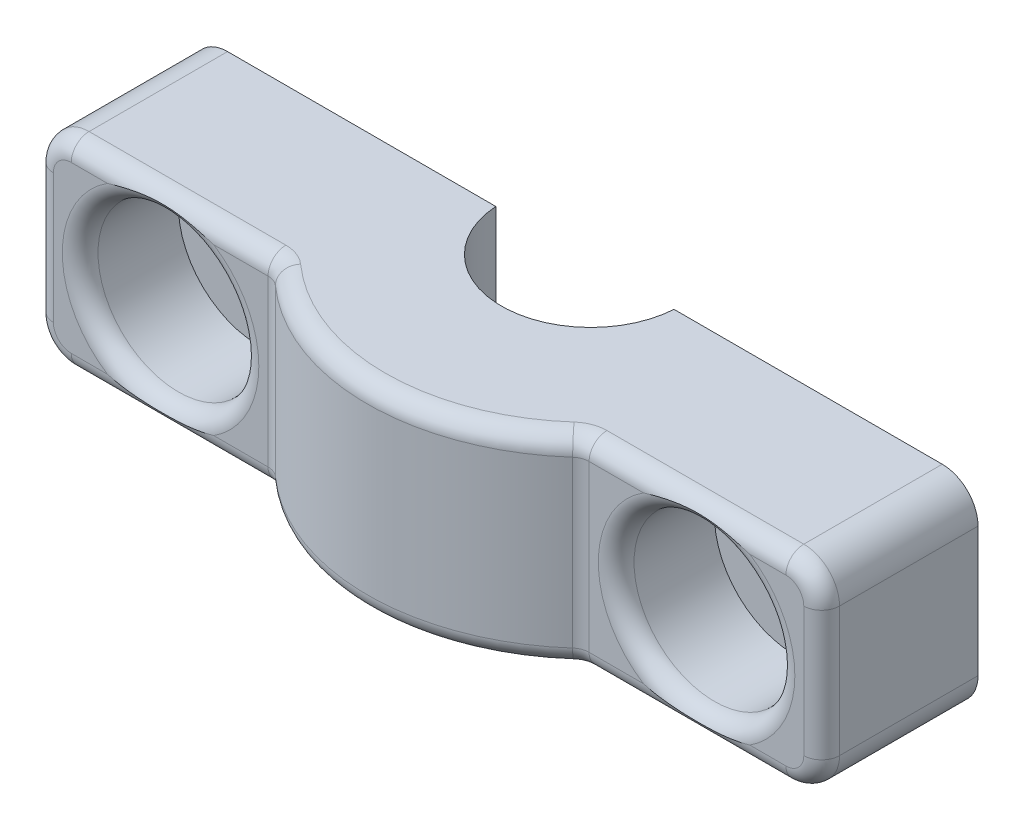
SolidWorks part; units mm, degrees
ref_plane "Front Plane" through (0, 0, 0) normal (0, 0, 1) x (1, 0, 0)
ref_plane "Top Plane" through (0, 0, 0) normal (0, 1, 0) x (1, 0, 0)
ref_plane "Right Plane" through (0, 0, 0) normal (1, 0, 0) x (0, 0, -1)
sketch "Sketch2" plane through (0, 0, 0) normal (0, 1, 0) x (1, 0, 0)
  line L0 (4.9994, -0.0762) -> (21.9999, -0.0762)
  line L1 (21.9999, -0.0762) -> (21.9999, -9.0762)
  line L2 (21.9999, -9.0762) -> (8.5949, -9.0762)
  line L3 (-4.9994, -0.0762) -> (-21.9999, -0.0762)
  line L4 (-21.9999, -0.0762) -> (-21.9999, -9.0762)
  line L5 (-21.9999, -9.0762) -> (-8.5949, -9.0762)
  arc A0 (-4.9994, -0.0762) -> (4.9994, -0.0762) centre (0, 0) ccw
  arc A1 (-8.5949, -9.0762) -> (8.5949, -9.0762) centre (0, 0) ccw
  dimension "D1" = 10
  dimension "D2" = 25
  dimension "D3" = 22
  dimension "D4" = 22
  dimension "D5" = 9
extrude "Boss-Extrude2" add sketch "Sketch2" along normal blind 11.25
sketch "Sketch3" plane through (0, 0, 9.0762) normal (0, 0, 1) x (1, 0, 0)
  line L0 (21.9999, 5.625) -> (-21.9999, 5.625) construction
  line L1 (21.9999, 11.25) -> (21.9999, 0) construction
  line L2 (-21.9999, 11.25) -> (-21.9999, 0) construction
  line L3 (8.5949, 11.25) -> (-8.5949, 11.25) construction
  line L4 (4.9994, 11.25) -> (-4.9994, 11.25) construction
  circle A0 centre (15, 5.625) radius 1.75
  circle A1 centre (-15, 5.625) radius 1.75
  point P10 (0, 11.25)
  point P13 (0, 11.25)
  dimension "D1" = 3.5
  dimension "D2" = 15
  dimension "D3" = 15
extrude "Cut-Extrude1" cut sketch "Sketch3" against normal blind 15
sketch "Sketch4" plane through (0, 0, 9.0762) normal (0, 0, 1) x (1, 0, 0)
  circle A0 centre (15, 5.625) radius 4.5
  circle A1 centre (-15, 5.625) radius 4.5
  dimension "D1" = 9
extrude "Cut-Extrude2" cut sketch "Sketch4" against normal offset from surface (5.5 mm away) 3.5 up to face at (16.75, 5.625, 0.0762)
fillet "Fillet1" radius 2 4 edges at (21.9999, 0, 4.5762) (21.9999, 11.25, 4.5762) (-21.9999, 0, 4.5762) (-21.9999, 11.25, 4.5762)
fillet "Fillet2" radius 1 16 edges at (14.2974, 11.25, 9.0762) (21.4141, 10.6642, 9.0762) (21.9999, 5.625, 9.0762) (21.4141, 0.5858, 9.0762) (-14.2974, 11.25, 9.0762) (-21.4141, 10.6642, 9.0762) (-21.9999, 5.625, 9.0762) (-21.4141, 0.5858, 9.0762) (19.5, 5.625, 9.0762) (-10.5, 5.625, 9.0762) (-8.5949, 5.625, 9.0762) (8.5949, 5.625, 9.0762) (0, 11.25, 12.5) (0, 0, 12.5) (14.2974, 0, 9.0762) (-14.2974, 0, 9.0762)
sketch "Sketch5" plane through (0, 11.25, 0) normal (0, 1, 0) x (1, 0, 0)
  line L0 (21.9999, -0.0762) -> (21.9999, -8.0762) construction
  line L1 (-21.9999, -0.0762) -> (21.9999, -0.0762)
  line L2 (-21.9999, -0.0762) -> (-21.9999, -0.3262)
  line L3 (-21.9999, -0.3262) -> (21.9999, -0.3262)
  line L4 (21.9999, -0.0762) -> (21.9999, -0.3262)
  dimension "D1" = 0.25
extrude "Cut-Extrude3" cut sketch "Sketch5" against normal blind 20
